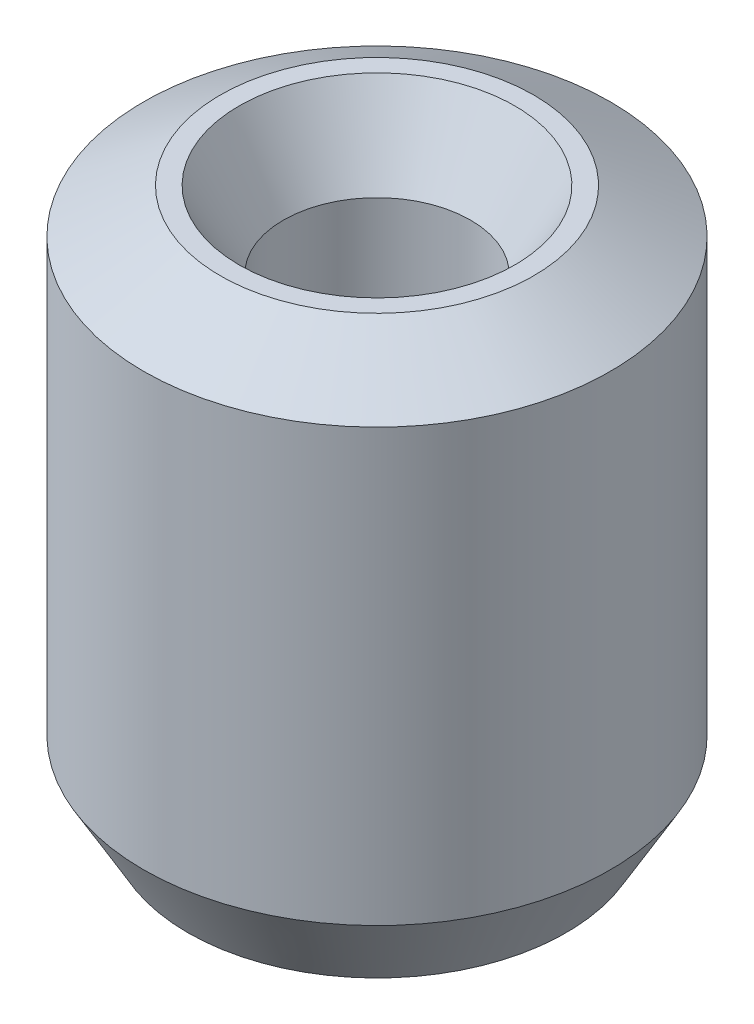
SolidWorks part; units mm, degrees
ref_plane "Front Plane" through (0, 0, 0) normal (0, 0, 1) x (1, 0, 0)
ref_plane "Top Plane" through (0, 0, 0) normal (0, 1, 0) x (1, 0, 0)
ref_plane "Right Plane" through (0, 0, 0) normal (1, 0, 0) x (0, 0, -1)
sketch "Sketch1" plane through (0, 0, 0) normal (0, 1, 0) x (1, 0, 0)
  circle A0 centre (0, 0) radius 10
  dimension "SLEEVE_OD" = 20
extrude "Boss-Extrude1" add sketch "Sketch1" along normal blind 23.6784
sketch "Sketch2" plane through (0, 0, 0) normal (0, 1, 0) x (1, 0, 0)
  circle A0 centre (0, 0) radius 4.0068
  dimension "BORE_D" = 8.0136
extrude "Cut-Extrude1" cut sketch "Sketch2" along normal through all
chamfer "Chamfer1" distance 1.8983 angle 60 4 edges at (0, 23.6784, 4.0068) (0, 0, 4.0068) (0, 0, 10) (0, 23.6784, 10) first distance on face at (0, 23.6784, 4.0068) first distance on face at (0, 0, 4.0068) first distance on face at (0, 23.6784, 10)
